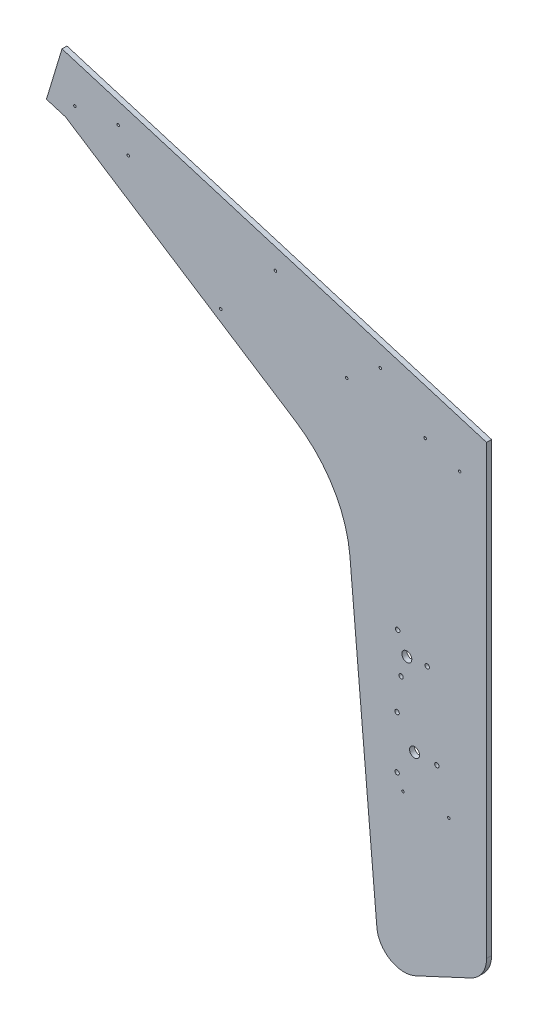
SolidWorks part; units mm, degrees
material "Beech"
ref_plane "Front Plane" through (0, 0, 0) normal (0, 0, 1) x (1, 0, 0)
ref_plane "Top Plane" through (0, 0, 0) normal (0, 1, 0) x (1, 0, 0)
ref_plane "Right Plane" through (0, 0, 0) normal (1, 0, 0) x (0, 0, -1)
sketch "Sketch1" plane through (0, 0, 0) normal (0, 0, 1) x (1, 0, 0)
  line L0 (-396.462, 396.5071) -> (138.3789, 234.6347) construction
  line L1 (134.7, 222.4793) -> (134.7, -217.5629) construction
  line L14 (-35.9297, 42.1538) -> (-1.5139, -351.2208)
  line L15 (48.0382, -379.8296) -> (118.2139, -347.1062)
  line L16 (138.3789, -315.4534) -> (138.3789, 254.5381)
  line L17 (138.3789, 254.5381) -> (-403.0991, 418.4193)
  line L18 (-403.0991, 418.4193) -> (-422.935, 352.8794)
  line L19 (-422.935, 352.8794) -> (-398.6241, 345.5216)
  line L20 (-398.6241, 345.5216) -> (-105.0266, 156.03)
  arc A6 (-35.9297, 42.1538) -> (-105.0266, 156.03) centre (-187.6695, 27.9835) ccw
  arc A7 (-1.5139, -351.2208) -> (48.0382, -379.8296) centre (33.2782, -348.1768) ccw
  arc A8 (118.2139, -347.1062) -> (138.3789, -315.4534) centre (103.4539, -315.4534) ccw
  dimension "D5" = 34.925
  dimension "D6" = 34.925
  dimension "D11" = 152.4
  dimension "D1" = 115
  dimension "D2" = 70
  dimension "D3" = 16
  dimension "D4" = 19.05
  dimension "D7" = 569.9915
  dimension "D8" = 602.715
  dimension "D9" = 34.925
  dimension "D10" = 105.1007
  dimension "D13" = 25.4
  dimension "D14" = 326.0484
  dimension "D15" = 226.5547
  dimension "D16" = 139.8928
  dimension "D17" = 77.4303
extrude "Boss-Extrude1" add sketch "Sketch1" along normal blind 6.35
hole_wizard "#10 Clearance Hole1" positions "Sketch3" profile "Sketch4" hole size "#10" standard "ANSI Inch" end condition through all
sketch "Sketch3" plane through (0, 0, 0) normal (0, 0, -1) x (-1, 0, 0)
  point P0 (-24.2517, -100.3519)
  point P3 (-24.2517, -167.0269)
  point P6 (-75.0517, -133.6894)
  point P9 (-29.3174, -58.2747)
  point P12 (-25.0263, -9.2271)
  point P15 (-62.6488, -30.6471)
sketch "Sketch4" plane through (24.2517, -100.3519, 0) normal (1, 0, 0) x (0, 1, 0)
  line L0 (0, 0) -> (0, 6.35)
  line L1 (0, 6.35) -> (2.8067, 6.35)
  line L2 (2.8067, 6.35) -> (2.8067, 0)
  line L5 (2.8067, 0) -> (0, 0)
  line L11 (0, -6.35) -> (0, 107.95) construction
  dimension "Thru Hole Dia." = 5.6134
  dimension "Thru Hole Depth" = 6.35
sketch "Sketch2" plane through (0, 0, 0) normal (0, 0, -1) x (-1, 0, 0)
  line L0 (-2.0267, -133.6894) -> (-59.1767, -133.6894) construction
  line L1 (-2.0267, -115.5093) -> (-2.0267, -151.8694) construction
  line L2 (-59.1767, -116.3297) -> (-59.1767, -151.0491) construction
  line L3 (-29.3174, -58.2747) -> (-25.0263, -9.2271) construction
  line L4 (-27.1718, -33.7509) -> (-62.6488, -30.6471) construction
  circle A0 centre (-46.4767, -133.6894) radius 6.35
  circle A1 centre (-36.6606, -32.9207) radius 6.35
  circle A2 centre (-24.2517, -100.3519) radius 2.8067 construction
  point P7 (-2.0267, -133.6894)
  point P11 (-59.1767, -133.6894)
  dimension "D1" = 12.7
  dimension "D2" = 12.7
  dimension "D3" = 22.225
  dimension "D4" = 9.525
extrude "Cut-Extrude1" cut sketch "Sketch2" against normal through all
hole_wizard "Hole1" positions "Sketch5" profile "Sketch6" legacy
sketch "Sketch5" plane through (277.2867, -215.2871, 12.7) normal (0, 0, 1) x (-0.09, 0.9959, 0)
  line L0 (54.6742, 260.7254) -> (44.8416, 151.8686) construction
  line L6 (458.2175, 188.8136) -> (426.7882, 117.3689) construction
  line L11 (443.4217, 288.0956) -> (513.4071, 262.4897) construction
  line L16 (479.186, 443.3317) -> (498.5551, 428.1819) construction
  line L19 (643.2075, 626.7743) -> (602.3132, 525.5573) construction
  line L24 (664.0363, 618.3589) -> (454.7061, 100.2486) construction
  line L28 (664.0363, 618.3589) -> (611.7037, 488.8313)
  line L29 (611.7037, 488.8313) -> (559.3712, 359.3037)
  line L30 (559.3712, 359.3037) -> (507.0387, 229.7761)
  line L31 (507.0387, 229.7761) -> (454.7061, 100.2486)
  point P12 (52.9605, 241.7526)
  point P14 (47.6978, 183.4898)
  point P29 (434.4591, 134.8062)
  point P31 (453.1036, 177.1887)
  point P48 (478.4144, 275.2927)
  point P60 (488.8705, 435.7568)
  point P79 (636.0712, 609.1114)
  point P81 (609.4494, 543.2202)
  point P98 (559.3712, 359.3037)
  point P100 (507.0387, 229.7761)
  point P112 (637.87, 553.5951)
sketch "Sketch6" plane through (-331.4463, 370.1954, 12.7) normal (1, 0, 0) x (0, -1, 0)
  line L0 (0, 0) -> (0, 32.7039)
  line L1 (0, 32.7039) -> (1.5875, 31.75)
  line L2 (1.5875, 31.75) -> (1.5875, 4.0177)
  line L3 (1.5875, 4.0177) -> (5.08, 0)
  line L4 (5.08, 0) -> (0, 0)
  line L5 (0, -14.3089) -> (0, 102.4216) construction
  line L6 (0, 32.7039) -> (-1.5875, 31.75) construction
  line L7 (-1.5875, 4.0177) -> (-5.08, 0) construction
  dimension "Diameter" = 3.175
  dimension "Depth" = 31.75
  dimension "C-Sink Diameter" = 10.16
  dimension "C-Sink Angle" = 82
  dimension "Drill Angle" = 118
